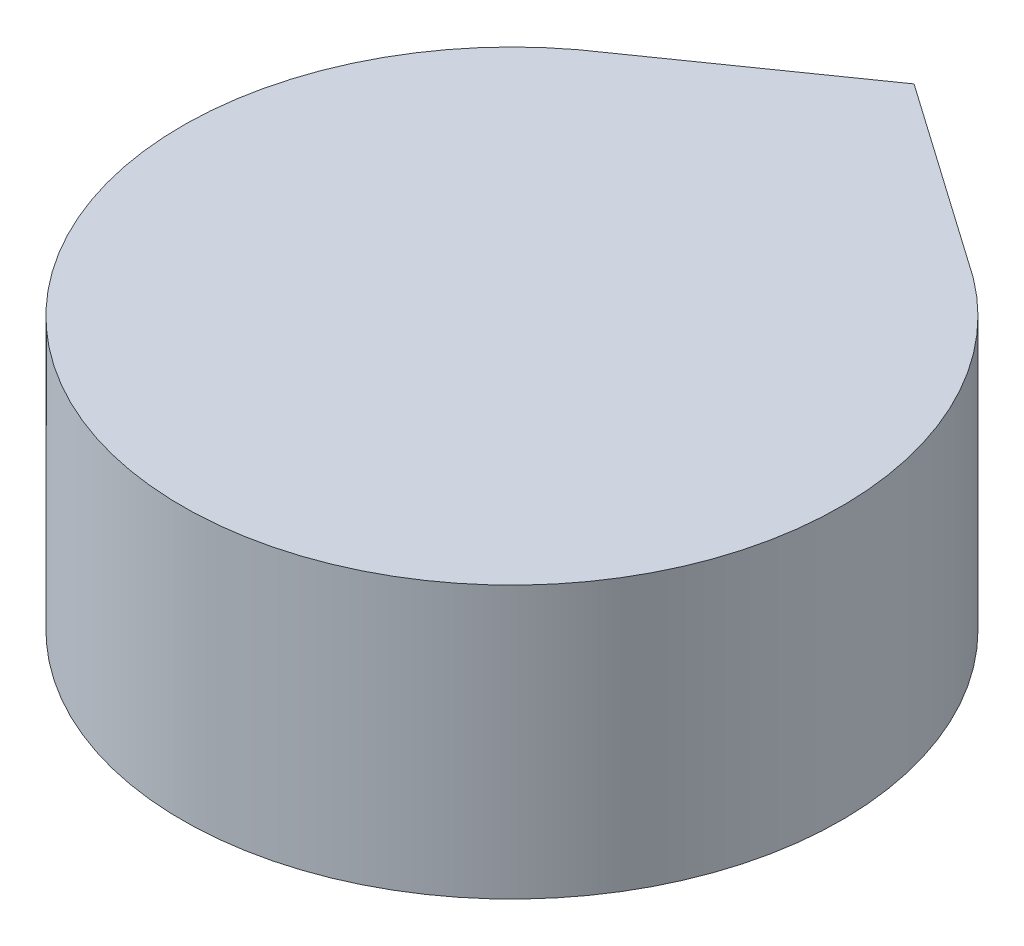
SolidWorks part; units mm, degrees
ref_plane "Front Plane" through (0, 0, 0) normal (0, 0, 1) x (1, 0, 0)
ref_plane "Top Plane" through (0, 0, 0) normal (0, 1, 0) x (1, 0, 0)
ref_plane "Right Plane" through (0, 0, 0) normal (1, 0, 0) x (0, 0, -1)
sketch "Sketch1" plane through (0, 0, 0) normal (0, 1, 0) x (1, 0, 0)
  circle A0 centre (0, 0) radius 3.25
extrude "Boss-Extrude1" add sketch "Sketch1" along normal blind 8 contours A0
sketch "Sketch2" plane through (0, 8, 0) normal (0, 1, 0) x (1, 0, 0)
  line L0 (-3, 1.25) -> (-3, 3.443)
  line L1 (0, 1.25) -> (-3, 1.25)
  line L2 (0, 1.25) -> (3, 1.25)
  line L3 (-3, 3.443) -> (3, 3.443)
  line L4 (3, 3.443) -> (3, 1.25)
  circle A0 centre (0, 0) radius 3.25 construction
extrude "Cut-Extrude1" cut sketch "Sketch2" against normal blind 8
sketch "Sketch3" plane through (0, 8, 0) normal (0, 1, 0) x (1, 0, 0)
  line L5 (-3, 1.25) -> (3, 1.25) construction
  line L7 (-0.75, 1.25) -> (0.75, 1.25)
  line L8 (-0.75, 1.25) -> (-0.75, -3.5083)
  line L9 (-0.75, -3.5083) -> (0.75, -3.5083)
  line L10 (0.75, 1.25) -> (0.75, -3.5083)
extrude "Cut-Extrude2" cut sketch "Sketch3" against normal blind 2
shell "Shell1" thickness 6.75 removed face at (0, 0, 1) outward yes
sketch "Sketch4" plane through (0, 14.75, 0) normal (0, 1, 0) x (1, 0, 0)
  line L1 (-13.3344, 10.0417) -> (13.8087, 10.0417)
  line L2 (-13.3344, 10.0417) -> (-13.3344, -12.1735)
  line L3 (-13.3344, -12.1735) -> (13.8087, -12.1735)
  line L4 (13.8087, 10.0417) -> (13.8087, -12.1735)
extrude "Cut-Extrude3" cut sketch "Sketch4" against normal blind 6.5
sketch "Sketch5" plane through (0, 0, -8) normal (0, 0, -1) x (-1, 0, 0)
  line L1 (-6, 8.25) -> (6, 8.25)
  line L2 (-6, 8.25) -> (-6, 0)
  line L3 (-6, 0) -> (6, 0)
  line L4 (6, 8.25) -> (6, 0)
extrude "Boss-Extrude2" add sketch "Sketch5" along normal blind 6
chamfer "Chamfer1" distance 6 angle 55 1 edges at (-6, 4.125, -14) first distance on face at (-6, 4.125, -11)
chamfer "Chamfer2" distance 6 angle 55 1 edges at (6, 4.125, -14) first distance on face at (6, 4.125, -11)
